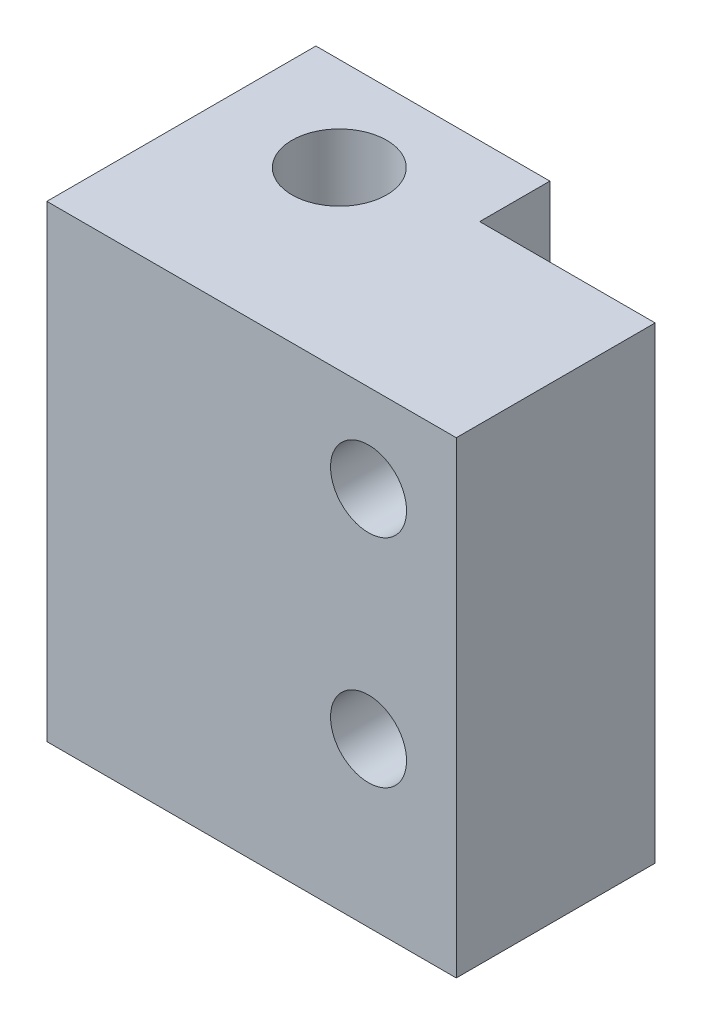
SolidWorks part; units mm, degrees
ref_plane "Front Plane" through (0, 0, 0) normal (0, 0, 1) x (1, 0, 0)
ref_plane "Top Plane" through (0, 0, 0) normal (0, 1, 0) x (1, 0, 0)
ref_plane "Right Plane" through (0, 0, 0) normal (1, 0, 0) x (0, 0, -1)
sketch "Sketch1" plane through (0, 0, 0) normal (0, 1, 0) x (1, 0, 0)
  line L5 (-10, -5.2575) -> (-10, 0.7425)
  line L6 (-10, 0.7425) -> (10, 0.7425)
  line L9 (25, -5.2575) -> (25, -22.2575)
  line L10 (0, -22.2575) -> (0, 0.7425) construction
  line L11 (-10, -5.2575) -> (-10, -22.2575)
  line L12 (10, 0.7425) -> (10, -5.2575)
  line L13 (10, -5.2575) -> (25, -5.2575)
  line L14 (-10, -22.2575) -> (25, -22.2575)
  point P2 (0, 0)
  dimension "D5" = 17
  dimension "D6" = 15
extrude "Boss-Extrude2" add sketch "Sketch1" along normal blind 40
sketch "Sketch3" plane through (0, 0, 0) normal (0, -1, 0) x (1, 0, 0)
  line L0 (0, -0.7425) -> (0, 22.2575) construction
  line L1 (10, -0.7425) -> (-10, -0.7425) construction
  circle A0 centre (0, 7.2575) radius 4.05
  dimension "D1" = 8.1
  dimension "D2" = 8
extrude "Cut-Extrude1" cut sketch "Sketch3" against normal blind 35
sketch "Sketch4" plane through (0, 0, 5.2575) normal (0, 0, -1) x (-1, 0, 0)
  line L0 (-25, 20) -> (-10, 20) construction
  line L1 (-25, 40) -> (-25, 0) construction
  line L2 (-10, 40) -> (-10, 0) construction
  line L3 (-17.5, 40) -> (-17.5, 0) construction
  line L4 (-25, 40) -> (-10, 40) construction
  line L5 (-25, 0) -> (-10, 0) construction
  circle A0 centre (-17.5, 26.0458) radius 3.25
  circle A2 centre (-17.5, 7.5353) radius 3.25
  dimension "D1" = 6.5
  dimension "D2" = 6.5
extrude "Cut-Extrude2" cut sketch "Sketch4" against normal up to next
sketch "Sketch5" plane through (0, 0, 0) normal (0, -1, 0) x (1, 0, 0)
  line L0 (0, -0.7425) -> (0, 22.2575) construction
  line L1 (10, -0.7425) -> (-10, -0.7425) construction
  line L2 (-10, 22.2575) -> (25, 22.2575) construction
sketch "Sketch6" plane through (0, 35, 0) normal (0, -1, 0) x (1, 0, 0)
  circle A0 centre (0, 7.2575) radius 1.5
  dimension "D1" = 3
extrude "Cut-Extrude3" cut sketch "Sketch6" against normal blind 10
mirror "Mirror4" about plane through (0, 0, 0) normal (0, 1, 0) of bodies 109 104
delete or keep bodies "Body-Delete/Keep 1" type keep bodies bodies 108
